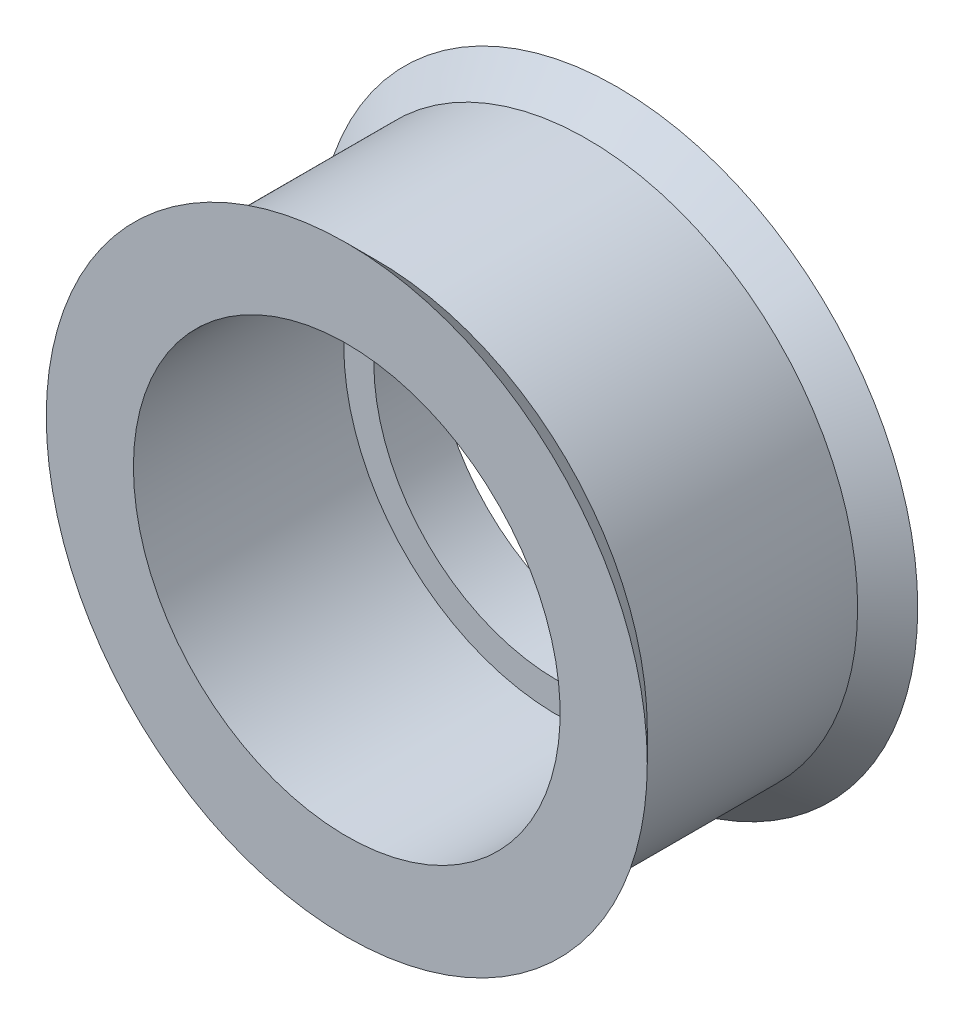
SolidWorks part; units mm, degrees
ref_plane "Front Plane" through (0, 0, 0) normal (0, 0, 1) x (1, 0, 0)
ref_plane "Top Plane" through (0, 0, 0) normal (0, 1, 0) x (1, 0, 0)
ref_plane "Right Plane" through (0, 0, 0) normal (1, 0, 0) x (0, 0, -1)
sketch "Sketch1" plane through (0, 0, 0) normal (0, 0, 1) x (1, 0, 0)
  circle A0 centre (0, 0) radius 7.1
  circle A1 centre (0, 0) radius 9
  circle A2 centre (0, 0) radius 10
  dimension "D1" = 14.2
  dimension "D2" = 18
  dimension "D3" = 20
extrude "Boss-Extrude1" add sketch "Sketch1" along normal mid plane 9 contours A1 A0 | A2 A1 region at (-8.7454, 0, 0) region at (-9.7172, 0, 0)
extrude "Cut-Extrude1" cut sketch "Sketch1<3>" against normal mid plane 7 contours A2 A1 region at (-9.7172, 0, 0)
sketch "Sketch1<3>" plane through (0, 0, 0) normal (0, 0, 1) x (1, 0, 0) same geometry as "Sketch1"
chamfer "Chamfer1" distance 1 angle 45 2 edges at (10, 0, 3.5) (10, 0, -3.5)
sketch "Sketch2" plane through (0, 0, -4.5) normal (0, 0, -1) x (-1, 0, 0)
  circle A0 centre (0, 0) radius 7.1 construction
  circle A1 centre (0, 0) radius 7.1
  circle A2 centre (0, 0) radius 6.1
  dimension "D1" = 1
extrude "Boss-Extrude2" add sketch "Sketch2" against normal blind 2
